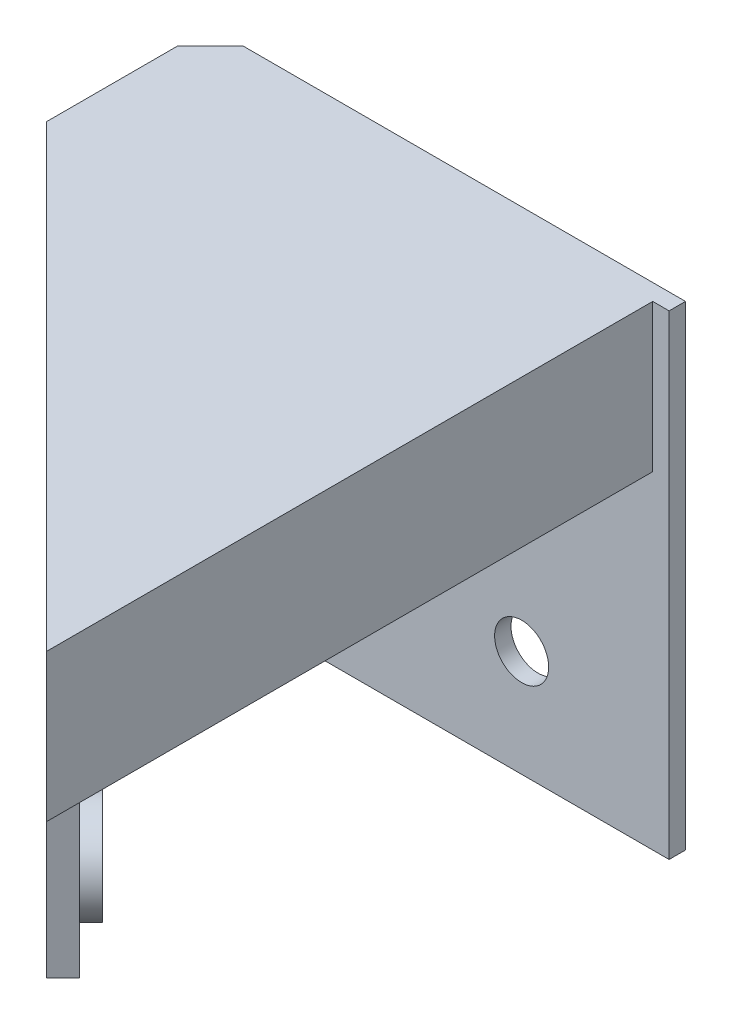
SolidWorks part; units mm, degrees
ref_plane "Front Plane" through (0, 0, 0) normal (0, 0, 1) x (1, 0, 0)
ref_plane "Top Plane" through (0, 0, 0) normal (0, 1, 0) x (1, 0, 0)
ref_plane "Right Plane" through (0, 0, 0) normal (1, 0, 0) x (0, 0, -1)
sketch "Sketch1" plane through (0, 0, 0) normal (0, 0, 1) x (1, 0, 0)
  line L1 (10.2499, -35.45) -> (-16.7501, -35.45)
  line L2 (10.2499, -35.45) -> (10.2499, -6.45)
  line L3 (10.2499, -6.45) -> (-16.7501, -6.45)
  line L4 (-16.7501, -35.45) -> (-16.7501, -6.45)
  point P0 (0, 0)
  point P9 (0, 0)
  dimension "D2" = 27
  dimension "D1" = 29
extrude "Boss-Extrude1" add sketch "Sketch1" along normal blind 1 contours L4 L1 L2 L3 region at (-3.2501, -20.95, 0)
sketch "Sketch4" plane through (-16.7501, 0, 0) normal (-1, 0, 0) x (0, 0, 1)
  line L0 (1, -35.45) -> (0, -35.45) construction
  line L1 (0, -6.45) -> (10, -6.45)
  line L2 (0, -6.45) -> (0, -35.45)
  line L3 (0, -35.45) -> (10, -35.45)
  line L4 (10, -6.45) -> (10, -35.45)
  dimension "D1" = 10
extrude "Boss-Extrude3" add sketch "Sketch4" along normal blind 2
sketch "Sketch5" plane through (0, -35.45, 0) normal (0, -1, 0) x (1, 0, 0)
  line L0 (-18.7501, 10) -> (-2.4866, 26.2635)
  line L1 (-2.4866, 26.2635) -> (-1.4866, 25.2635)
  line L2 (-1.4866, 25.2635) -> (-16.7501, 10)
  line L3 (-16.7501, 1) -> (-16.7501, 10) construction
  line L4 (-16.7501, 10) -> (-18.7501, 10)
  dimension "D1" = 135
  dimension "D2" = 23
extrude "Boss-Extrude4" add sketch "Sketch5" against normal up to surface (29 mm away) up to face at (-8.4167, -6.45, 3.6667)
sketch "Sketch6" plane through (-13.375, 0, 13.375) normal (0.7071, 0, -0.7071) x (-0.7071, 0, -0.7071)
  line L0 (-16.8128, -6.45) -> (-16.8128, -35.45) construction
  line L2 (4.773, -35.45) -> (-16.8128, -35.45) construction
  line L3 (-11.8128, -32.45) -> (-11.8128, -18.45) construction
  circle A1 centre (-11.8128, -32.45) radius 1.65
  circle A2 centre (-11.8128, -18.45) radius 1.65
  dimension "D1" = 14
  dimension "D4" = 5
  dimension "D5" = 3
  dimension "D6" = 3.3
extrude "Cut-Extrude1" cut sketch "Sketch6" against normal blind 2
chamfer "Chamfer1" distance 1 angle 45 1 edges at (-16.7501, -20.95, 1)
sketch "Sketch7" plane through (0, 0, 1) normal (0, 0, 1) x (1, 0, 0)
  line L0 (-18.7501, -6.45) -> (-2.4866, -6.45) construction
  line L1 (-14.7501, -14.45) -> (8.2499, -14.45)
  line L2 (-14.7501, -14.45) -> (-14.7501, -7.45)
  line L3 (-14.7501, -7.45) -> (8.2499, -7.45)
  line L4 (8.2499, -14.45) -> (8.2499, -7.45)
  line L5 (-14.7501, -14.45) -> (8.2499, -7.45) construction
  line L6 (-14.7501, -7.45) -> (8.2499, -14.45) construction
  line L14 (10.2499, -35.45) -> (10.2499, -6.45) construction
  line L15 (-18.7501, -6.45) -> (-18.7501, -35.45) construction
  point P0 (-3.2501, -10.95)
  point P5 (-3.2501, -10.95)
  dimension "D1" = 4
  dimension "D2" = 7
  dimension "D3" = 1
  dimension "D4" = 2
extrude "Cut-Extrude3" cut sketch "Sketch7" against normal up to surface (1 mm away) and the other way up to surface up to face at (-4.2501, -20.95, 0) other way up to face at (-4.8554, -18.45, 23.8946)
sketch "Sketch9" plane through (0, 0, 0) normal (0, 0, -1) x (-1, 0, 0)
  line L0 (-10.2499, -20.95) -> (18.7501, -20.95) construction
  line L1 (-9.2499, -15.45) -> (18.7501, -15.45)
  line L2 (-9.2499, -15.45) -> (-9.2499, -6.45)
  line L3 (-9.2499, -6.45) -> (18.7501, -6.45)
  line L4 (18.7501, -15.45) -> (18.7501, -6.45)
  line L5 (-10.2499, -35.45) -> (-10.2499, -6.45) construction
  line L6 (-8.2499, -14.45) -> (14.7501, -14.45) construction
  line L9 (14.7501, -7.45) -> (-8.2499, -7.45) construction
  line L10 (-8.2499, -7.45) -> (-8.2499, -14.45) construction
  line L11 (-8.2499, -14.45) -> (14.7501, -14.45)
  line L12 (-8.2499, -14.45) -> (-8.2499, -7.45)
  line L13 (-8.2499, -7.45) -> (14.7501, -7.45)
  line L14 (14.7501, -14.45) -> (14.7501, -7.45)
  line L15 (-8.2499, -14.45) -> (14.7501, -7.45) construction
  line L16 (-8.2499, -7.45) -> (14.7501, -14.45) construction
  line L17 (18.7501, -6.45) -> (18.7501, -35.45) construction
  point P0 (12.425, 0)
  point P13 (3.2501, -10.95)
  dimension "D1" = 1
  dimension "D2" = 1
  dimension "D4" = 1
extrude "Boss-Extrude6" add sketch "Sketch9" against normal up to surface (38 mm away) up to face at (-9.6183, -15.95, 19.1317)
chamfer "Chamfer3" distance 2 angle 45 1 edges at (-18.7501, -20.95, 0)
sketch "Sketch10" plane through (0, 0, 1) normal (0, 0, 1) x (1, 0, 0)
  line L0 (10.2499, -35.45) -> (-15.7501, -35.45) construction
  line L1 (10.2499, -35.45) -> (10.2499, -6.45) construction
  circle A0 centre (1.2499, -28.95) radius 1.65
  dimension "D1" = 6.5
  dimension "D2" = 9
  dimension "D3" = 3.3
extrude "Cut-Extrude4" cut sketch "Sketch10" against normal blind 10
sketch "Sketch11" plane through (0, 0, 0) normal (0, 0, -1) x (-1, 0, 0)
  line L0 (-8.2499, -14.45) -> (14.7501, -14.45) construction
  line L1 (-6.1499, -14.45) -> (-3.3499, -14.45)
  line L2 (-6.1499, -14.45) -> (-6.1499, -17.35)
  line L3 (-6.1499, -17.35) -> (-3.3499, -17.35)
  line L4 (-3.3499, -14.45) -> (-3.3499, -17.35)
  line L5 (-10.2499, -35.45) -> (-10.2499, -6.45) construction
  line L6 (9.8501, -14.45) -> (12.6501, -14.45)
  line L7 (9.8501, -14.45) -> (9.8501, -17.35)
  line L8 (9.8501, -17.35) -> (12.6501, -17.35)
  line L9 (12.6501, -14.45) -> (12.6501, -17.35)
  line L10 (16.7501, -35.45) -> (16.7501, -6.45) construction
  dimension "D1" = 2.8
  dimension "D2" = 2.9
  dimension "D3" = 4.1
  dimension "D4" = 4.1
  dimension "D5" = 2.8
  dimension "D6" = 2.9
extrude "Boss-Extrude7" add sketch "Sketch11" along normal blind 3
sketch "Sketch12" plane through (-13.375, 0, 13.375) normal (0.7071, 0, -0.7071) x (-0.7071, 0, -0.7071)
  circle A0 centre (-11.8128, -18.45) radius 2.95
  circle A1 centre (-11.8128, -18.45) radius 1.65
  circle A2 centre (-11.8128, -32.45) radius 1.65
  circle A3 centre (-11.8128, -32.45) radius 2.95
  dimension "D1" = 1.3
  dimension "D2" = 1.3
extrude "Boss-Extrude8" add sketch "Sketch12" along normal blind 1
